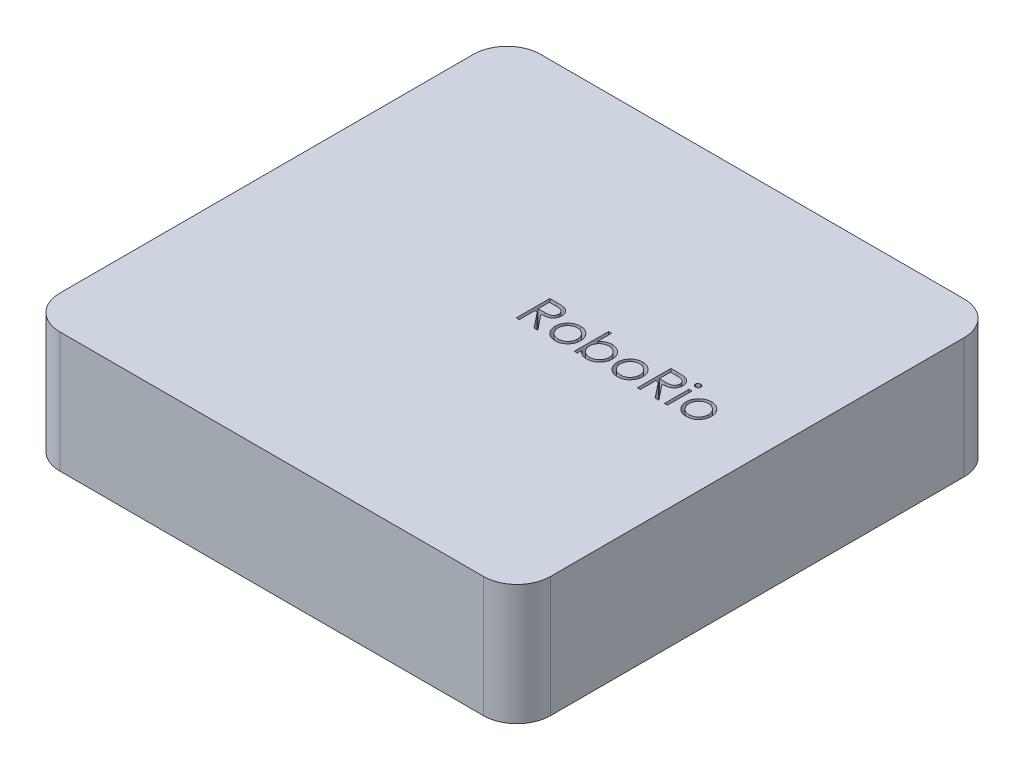
SolidWorks part; units mm, degrees
ref_plane "Front Plane" through (0, 0, 0) normal (0, 0, 1) x (1, 0, 0)
ref_plane "Top Plane" through (0, 0, 0) normal (0, 1, 0) x (1, 0, 0)
ref_plane "Right Plane" through (0, 0, 0) normal (1, 0, 0) x (0, 0, -1)
sketch "Sketch1" plane through (0, 0, 0) normal (0, 1, 0) x (1, 0, 0)
  line L1 (-73.25, 71.75) -> (73.25, 71.75)
  line L2 (-73.25, 71.75) -> (-73.25, -71.75)
  line L3 (-73.25, -71.75) -> (73.25, -71.75)
  line L4 (73.25, 71.75) -> (73.25, -71.75)
  point P4 (0, -71.75)
  point P6 (-73.25, 0)
  dimension "D1" = 146.5
  dimension "D2" = 143.5
extrude "Boss-Extrude1" add sketch "Sketch1" along normal blind 36 contours L1 L4 L3 L2
fillet "Fillet1" radius 10 4 edges at (73.25, 18, 71.75) (73.25, 18, -71.75) (-73.25, 18, -71.75) (-73.25, 18, 71.75)
sketch "Sketch2" plane through (0, 36, 0) normal (0, 1, 0) x (1, 0, 0)
  text T0 "RoboRio" font "Century Gothic" height 10
  point P1 (0, 0)
  point P3 (0, 0)
extrude "Cut-Extrude1" cut sketch "Sketch2" against normal blind 10
